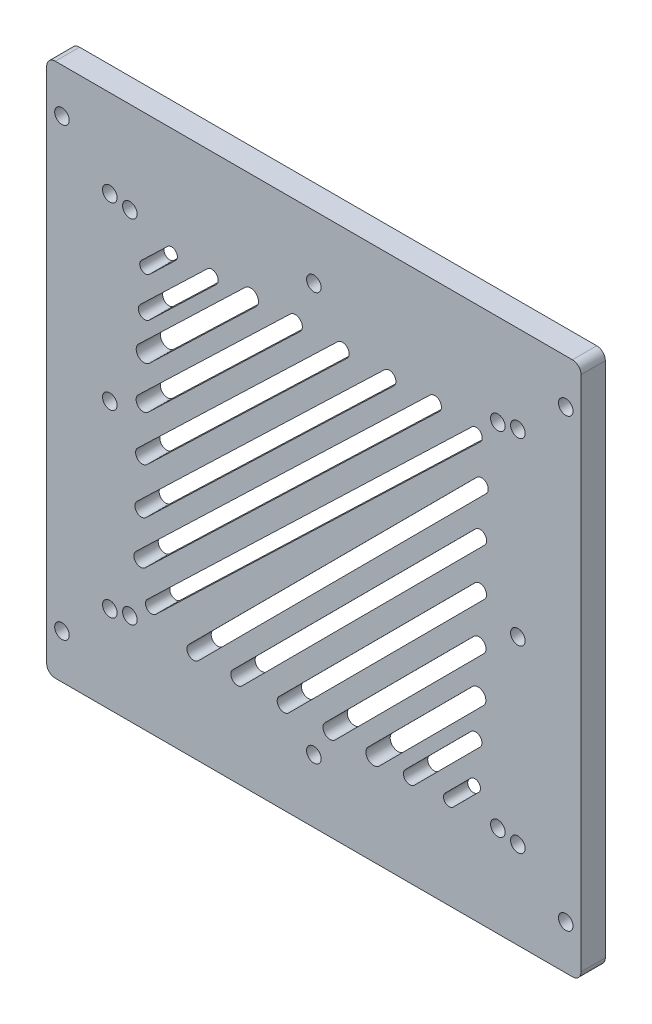
SolidWorks part; units mm, degrees
ref_plane "Front Plane" through (0, 0, 0) normal (0, 0, 1) x (1, 0, 0)
ref_plane "Top Plane" through (0, 0, 0) normal (0, 1, 0) x (1, 0, 0)
ref_plane "Right Plane" through (0, 0, 0) normal (1, 0, 0) x (0, 0, -1)
sketch "Sketch1" plane through (0, 0, 0) normal (0, 0, 1) x (1, 0, 0)
  line L0 (17.125, 18.82) -> (92.875, 18.82) construction
  line L1 (0, 73.4) -> (110, 73.4) construction
  line L2 (1.7755, 0) -> (108.2245, 0)
  line L3 (0, 1.7755) -> (0, 108.2245)
  line L4 (1.7755, 110) -> (108.2245, 110)
  line L5 (110, 1.7755) -> (110, 108.2245)
  line L6 (0, 36.6) -> (110, 36.6) construction
  line L7 (34, 110) -> (34, 0) construction
  line L8 (76, 110) -> (76, 0) construction
  line L9 (92.875, 91.18) -> (92.875, 18.82) construction
  line L10 (17.125, 18.82) -> (17.125, 91.18) construction
  line L11 (17.125, 91.18) -> (92.875, 91.18) construction
  arc A0 (1.7755, 0) -> (0, 1.7755) centre (1.7755, 1.7755) cw
  arc A1 (108.2245, 0) -> (110, 1.7755) centre (108.2245, 1.7755) ccw
  arc A2 (108.2245, 110) -> (110, 108.2245) centre (108.2245, 108.2245) cw
  arc A3 (0, 108.2245) -> (1.7755, 110) centre (1.7755, 108.2245) cw
  circle A4 centre (3.15, 100.9) radius 1.5
  circle A5 centre (13, 92) radius 1.5
  circle A6 centre (106.85, 100.9) radius 1.5
  circle A7 centre (97, 92) radius 1.5
  circle A8 centre (3.15, 9.1) radius 1.5
  circle A9 centre (13, 18) radius 1.5
  circle A10 centre (106.85, 9.1) radius 1.5
  circle A11 centre (97, 18) radius 1.5
  circle A12 centre (17.125, 91.18) radius 1.5
  circle A13 centre (92.875, 91.18) radius 1.5
  circle A14 centre (17.125, 18.82) radius 1.5
  circle A15 centre (92.875, 18.82) radius 1.5
  point P7 (0, 0)
  point P10 (110, 0)
  point P15 (0, 110)
  point P24 (13, 92)
  point P25 (97, 92)
  point P26 (97, 18)
  point P27 (13, 18)
  point P28 (3.15, 100.9)
  point P29 (106.85, 100.9)
  point P30 (106.85, 9.1)
  point P31 (3.15, 9.1)
  dimension "D3" = 1.7755
  dimension "D24" = 75.75
  dimension "D1" = 110
  dimension "D2" = 110
  dimension "D4" = 36.6
  dimension "D5" = 36.6
  dimension "D6" = 34
  dimension "D7" = 34
  dimension "D8" = 18
  dimension "D9" = 18
  dimension "D10" = 18
  dimension "D11" = 18
  dimension "D12" = 13
  dimension "D13" = 13
  dimension "D14" = 13
  dimension "D15" = 13
  dimension "D16" = 8.9
  dimension "D17" = 8.9
  dimension "D18" = 8.9
  dimension "D19" = 8.9
  dimension "D20" = 9.85
  dimension "D21" = 9.85
  dimension "D22" = 9.85
  dimension "D23" = 9.85
  dimension "D25" = 72.36
  dimension "D26" = 18.82
  dimension "D27" = 17.125
extrude "Boss-Extrude1" add sketch "Sketch1" along normal blind 5 contours L4 A2 L5 A1 L2 A0 L3 A3
extrude "Cut-Extrude1" cut sketch "Sketch1<3>" along normal blind 5 contours A6 | A7 | A5 | A4 | A10 | A11 | A9 | A8 | A12 | A13 | A14 | A15
sketch "Sketch1<3>" plane through (0, 0, 0) normal (0, 0, 1) x (1, 0, 0) same geometry as "Sketch1"
sketch "Sketch2" plane through (0, 0, 0) normal (0, 0, -1) x (-1, 0, 0)
  text T0 "<b>FRONT</b>\r\n" font "Century Gothic" height 6
  text T1 "<b>BACK</b>" font "Century Gothic" height 6
extrude "Boss-Extrude2" add sketch "Sketch2" along normal blind 1.5
sketch "Sketch3" plane through (0, 0, 5) normal (0, 0, 1) x (1, 0, 0)
  line L0 (1.7755, 110) -> (108.2245, 110) construction
  line L1 (0, 1.7755) -> (0, 108.2245) construction
  line L2 (110, 1.7755) -> (110, 108.2245) construction
  line L3 (1.7755, 0) -> (108.2245, 0) construction
  circle A0 centre (55, 97) radius 1.5
  circle A1 centre (97, 55) radius 1.5
  circle A2 centre (13, 55) radius 1.5
  circle A3 centre (55, 13) radius 1.5
  point P0 (55, 97)
  point P1 (55, 13)
  point P2 (97, 55)
  point P3 (13, 55)
  dimension "D5" = 55
  dimension "D6" = 55
  dimension "D7" = 55
  dimension "D8" = 55
  dimension "D1" = 13
  dimension "D2" = 13
  dimension "D3" = 13
  dimension "D4" = 13
extrude "Cut-Extrude3" cut sketch "Sketch3" against normal blind 10 contours A0 | A1 | A3 | A2
sketch "Sketch5" plane through (0, 0, 0) normal (0, 0, -1) x (-1, 0, 0)
  line L0 (-88.4105, 86.7995) -> (-21.5895, 22.6401) construction
  line L1 (-87.5428, 87.7032) -> (-20.7218, 23.5438)
  line L2 (-89.2782, 85.8958) -> (-22.4572, 21.7364)
  line L3 (-79.884, 88.0725) -> (-19.3385, 29.9387) construction
  line L4 (-78.9308, 89.0653) -> (-18.3853, 30.9314)
  line L5 (-80.8372, 87.0798) -> (-20.2917, 28.9459)
  line L6 (-70.5296, 87.9429) -> (-19.5098, 38.9554) construction
  line L7 (-69.5895, 88.922) -> (-18.5697, 39.9344)
  line L8 (-71.4696, 86.9639) -> (-20.4498, 37.9763)
  line L9 (-60.8792, 88.0725) -> (-19.6916, 48.5255) construction
  line L10 (-59.9188, 89.0728) -> (-18.7312, 49.5258)
  line L11 (-61.8397, 87.0722) -> (-20.652, 47.5252)
  line L12 (-51.1709, 88.0725) -> (-19.872, 58.0203) construction
  line L13 (-50.1595, 89.1259) -> (-18.8606, 59.0737)
  line L14 (-52.1823, 87.0192) -> (-20.8834, 56.967)
  line L15 (-41.9856, 88.0725) -> (-20.0426, 67.0036) construction
  line L16 (-40.8719, 89.2324) -> (-18.929, 68.1635)
  line L17 (-43.0993, 86.9127) -> (-21.1563, 65.8437)
  line L18 (-34, 87.7032) -> (-20.1839, 74.4374) construction
  line L19 (-33.0871, 88.654) -> (-19.271, 75.3882)
  line L20 (-34.9129, 86.7525) -> (-21.0967, 73.4867)
  line L21 (-25.7226, 87.7032) -> (-20.3346, 82.5298) construction
  line L22 (-24.9081, 88.5516) -> (-19.52, 83.3782)
  line L23 (-26.5372, 86.8549) -> (-21.1491, 81.6814)
  line L24 (-88.4105, 86.7995) -> (-21.5895, 22.6401) construction
  line L25 (-88.4105, 86.7995) -> (-90.7955, 89.1396) construction
  line L26 (-88.1233, 24.1058) -> (-82.8485, 18.817) construction
  line L27 (-88.9561, 23.2752) -> (-83.6812, 17.9864)
  line L28 (-87.2906, 24.9363) -> (-82.0157, 19.6475)
  line L29 (-88.2806, 32.3817) -> (-74.7547, 18.82) construction
  line L30 (-89.2138, 31.4509) -> (-75.6879, 17.8892)
  line L31 (-87.3473, 33.3124) -> (-73.8215, 19.7508)
  line L32 (-88.8015, 40.3588) -> (-67.3196, 18.82) construction
  line L33 (-89.94, 39.2233) -> (-68.4581, 17.6845)
  line L34 (-87.663, 41.4943) -> (-66.1811, 19.9555)
  line L35 (-88.9759, 49.5425) -> (-58.3346, 18.82) construction
  line L36 (-90.0099, 48.5112) -> (-59.3686, 17.7888)
  line L37 (-87.942, 50.5737) -> (-57.3007, 19.8512)
  line L38 (-89.1604, 59.249) -> (-48.8381, 18.82) construction
  line L39 (-90.1422, 58.2698) -> (-49.82, 17.8407)
  line L40 (-88.1785, 60.2283) -> (-47.8562, 19.7993)
  line L41 (-89.214, 68.9001) -> (-39.2662, 18.82) construction
  line L42 (-90.1751, 67.9416) -> (-40.2273, 17.8615)
  line L43 (-88.253, 69.8586) -> (-38.3052, 19.7785)
  line L44 (-89.5213, 78.2504) -> (-30.2479, 18.82) construction
  line L45 (-90.4958, 77.2785) -> (-31.2224, 17.8481)
  line L46 (-88.5469, 79.2223) -> (-29.2734, 19.7919)
  line L47 (-17.125, 18.82) -> (-92.875, 18.82) construction
  line L48 (-34, 110) -> (-34, 0) construction
  arc A0 (-87.5428, 87.7032) -> (-89.2782, 85.8958) centre (-88.4105, 86.7995) ccw
  arc A1 (-22.4572, 21.7364) -> (-20.7218, 23.5438) centre (-21.5895, 22.6401) ccw
  arc A2 (-78.9308, 89.0653) -> (-80.8372, 87.0798) centre (-79.884, 88.0725) ccw
  arc A3 (-20.2917, 28.9459) -> (-18.3853, 30.9314) centre (-19.3385, 29.9387) ccw
  arc A4 (-69.5895, 88.922) -> (-71.4696, 86.9639) centre (-70.5296, 87.9429) ccw
  arc A5 (-20.4498, 37.9763) -> (-18.5697, 39.9344) centre (-19.5098, 38.9554) ccw
  arc A6 (-59.9188, 89.0728) -> (-61.8397, 87.0722) centre (-60.8792, 88.0725) ccw
  arc A7 (-20.652, 47.5252) -> (-18.7312, 49.5258) centre (-19.6916, 48.5255) ccw
  arc A8 (-50.1595, 89.1259) -> (-52.1823, 87.0192) centre (-51.1709, 88.0725) ccw
  arc A9 (-20.8834, 56.967) -> (-18.8606, 59.0737) centre (-19.872, 58.0203) ccw
  arc A10 (-40.8719, 89.2324) -> (-43.0993, 86.9127) centre (-41.9856, 88.0725) ccw
  arc A11 (-21.1563, 65.8437) -> (-18.929, 68.1635) centre (-20.0426, 67.0036) ccw
  arc A12 (-33.0871, 88.654) -> (-34.9129, 86.7525) centre (-34, 87.7032) ccw
  arc A13 (-21.0967, 73.4867) -> (-19.271, 75.3882) centre (-20.1839, 74.4374) ccw
  arc A14 (-24.9081, 88.5516) -> (-26.5372, 86.8549) centre (-25.7226, 87.7032) ccw
  arc A15 (-21.1491, 81.6814) -> (-19.52, 83.3782) centre (-20.3346, 82.5298) ccw
  arc A16 (-88.9561, 23.2752) -> (-87.2906, 24.9363) centre (-88.1233, 24.1058) cw
  arc A17 (-82.0157, 19.6475) -> (-83.6812, 17.9864) centre (-82.8485, 18.817) cw
  arc A18 (-89.2138, 31.4509) -> (-87.3473, 33.3124) centre (-88.2806, 32.3817) cw
  arc A19 (-73.8215, 19.7508) -> (-75.6879, 17.8892) centre (-74.7547, 18.82) cw
  arc A20 (-89.94, 39.2233) -> (-87.663, 41.4943) centre (-88.8015, 40.3588) cw
  arc A21 (-66.1811, 19.9555) -> (-68.4581, 17.6845) centre (-67.3196, 18.82) cw
  arc A22 (-90.0099, 48.5112) -> (-87.942, 50.5737) centre (-88.9759, 49.5425) cw
  arc A23 (-57.3007, 19.8512) -> (-59.3686, 17.7888) centre (-58.3346, 18.82) cw
  arc A24 (-90.1422, 58.2698) -> (-88.1785, 60.2283) centre (-89.1604, 59.249) cw
  arc A25 (-47.8562, 19.7993) -> (-49.82, 17.8407) centre (-48.8381, 18.82) cw
  arc A26 (-90.1751, 67.9416) -> (-88.253, 69.8586) centre (-89.214, 68.9001) cw
  arc A27 (-38.3052, 19.7785) -> (-40.2273, 17.8615) centre (-39.2662, 18.82) cw
  arc A28 (-90.4958, 77.2785) -> (-88.5469, 79.2223) centre (-89.5213, 78.2504) cw
  arc A29 (-29.2734, 19.7919) -> (-31.2224, 17.8481) centre (-30.2479, 18.82) cw
  point P2 (-55, 54.7198)
  point P7 (-49.6113, 59.0056)
  point P14 (-45.0197, 63.4491)
  point P21 (-40.2854, 68.299)
  point P28 (-35.5214, 73.0464)
  point P35 (-31.0141, 77.5381)
  point P42 (-27.0919, 81.0703)
  point P49 (-23.0286, 85.1165)
  point P61 (-85.4859, 21.4614)
  point P68 (-81.5176, 25.6008)
  point P75 (-78.0605, 29.5894)
  point P82 (-73.6553, 34.1812)
  point P89 (-68.9992, 39.0345)
  point P96 (-64.2401, 43.86)
  point P103 (-59.8846, 48.5352)
extrude "Cut-Extrude4" cut sketch "Sketch5" against normal blind 5
